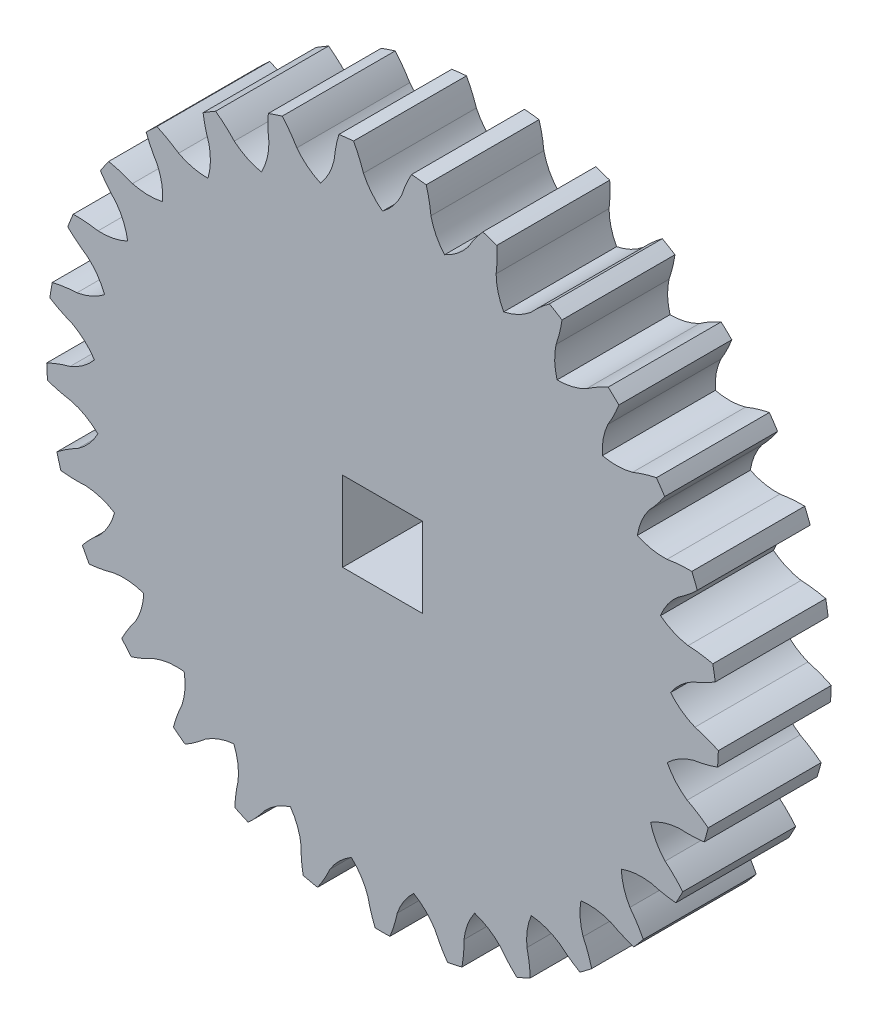
SolidWorks part; units mm, degrees
ref_plane "Front Plane" through (0, 0, 0) normal (0, 0, 1) x (1, 0, 0)
ref_plane "Top Plane" through (0, 0, 0) normal (0, 1, 0) x (1, 0, 0)
ref_plane "Right Plane" through (0, 0, 0) normal (1, 0, 0) x (0, 0, -1)
sketch "Sketch1" plane through (0, 0, 0) normal (0, 0, 1) x (1, 0, 0)
  line L1 (3.5355, -3.5355) -> (-3.5355, -3.5355)
  line L2 (3.5355, -3.5355) -> (3.5355, 3.5355)
  line L3 (3.5355, 3.5355) -> (-3.5355, 3.5355)
  line L4 (-3.5355, -3.5355) -> (-3.5355, 3.5355)
  line L5 (3.5355, -3.5355) -> (-3.5355, 3.5355) construction
  line L6 (3.5355, 3.5355) -> (-3.5355, -3.5355) construction
  circle A0 centre (0, 0) radius 29.75
  circle A1 centre (0, 0) radius 5 construction
  dimension "D1" = 59.5
  dimension "D2" = 10
extrude "Boss-Extrude1" add sketch "Sketch1" along normal blind 10
sketch "Sketch2" plane through (0, 0, 0) normal (0, 0, 1) x (1, 0, 0)
  line L0 (0, 0) -> (0, 36.6661) construction
  arc A25 (0, 25.5436) -> (-1.6909, 27.6123) centre (3.2409, 29.9179) cw
  arc A26 (-1.6909, 27.6123) -> (-6.9218, 34.1) centre (-12.7926, 24.0138) ccw
  arc A27 (-6.9218, 34.1) -> (0, 36.6661) centre (0.5436, 24.5815) cw
  arc A28 (6.9218, 34.1) -> (0, 36.6661) centre (-0.5436, 24.5815) ccw
  arc A29 (1.6909, 27.6123) -> (6.9218, 34.1) centre (12.7926, 24.0138) cw
  arc A30 (0, 25.5436) -> (1.6909, 27.6123) centre (-3.2409, 29.9179) ccw
extrude "Cut-Extrude1" cut sketch "Sketch2" along normal through all
pattern_circular "CirPattern1" count 29 over 360 about axis through (0, 0, 10) along (0, 0, -1) of "Cut-Extrude1"
sketch "Sketch3" plane through (0, 0, 0) normal (0, 0, 1) x (1, 0, 0)
  circle A0 centre (0, 0) radius 29.75
  dimension "D1" = 59.5
